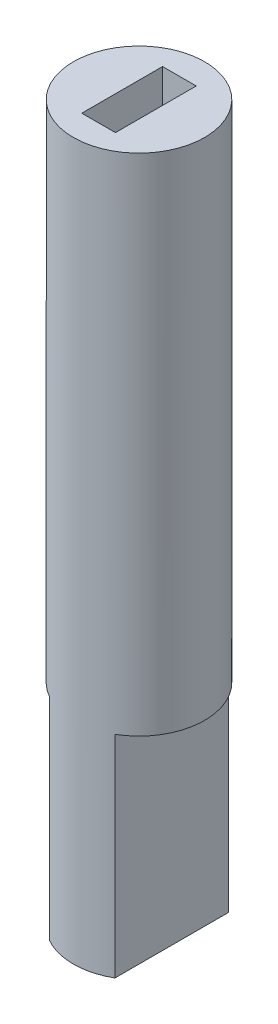
SolidWorks part; units mm, degrees
material "AISI 304"
ref_plane "Front Plane" through (0, 0, 0) normal (0, 0, 1) x (1, 0, 0)
ref_plane "Top Plane" through (0, 0, 0) normal (0, 1, 0) x (1, 0, 0)
ref_plane "Right Plane" through (0, 0, 0) normal (1, 0, 0) x (0, 0, -1)
sketch "Sketch1" plane through (0, 0, 0) normal (0, 1, 0) x (1, 0, 0)
  circle A0 centre (0, 0) radius 30
  dimension "D1" = 60
extrude "Boss-Extrude1" add sketch "Sketch1" along normal blind 200
sketch "Sketch2" plane through (0, 200, 0) normal (0, 1, 0) x (1, 0, 0)
  circle A0 centre (0, -50) radius 4
  circle A2 centre (0, 0) radius 30 construction
  dimension "D1" = 8
  dimension "D2" = 50
extrude "Boss-Extrude2" add sketch "Sketch2" against normal blind 80 from offset 60 separate body offset against normal yes
sketch "Sketch4" plane through (0, 140, 0) normal (0, 1, 0) x (1, 0, 0)
  line L6 (-2.9328, -47.28) -> (40.9159, 0)
  line L7 (2.9328, -52.72) -> (51.8267, 0)
  line L8 (40.9159, 0) -> (6, 37.6481)
  line L9 (51.8267, 0) -> (11.8657, 43.0881)
  line L10 (6, 37.6481) -> (11.8657, 43.0881)
  circle A0 centre (0, -50) radius 4 construction
  circle A1 centre (0, 0) radius 30 construction
  arc A2 (2.9328, -52.72) -> (-2.9328, -47.28) centre (0, -50) ccw
  dimension "D2" = 6
  dimension "D4" = 8
  dimension "D5" = 8
  dimension "D6" = 8
extrude "Boss-Extrude3" add sketch "Sketch4" against normal blind 10
sketch "Sketch5" plane through (0, 60, 0) normal (0, -1, 0) x (1, 0, 0)
  line L0 (6, -37.6481) -> (11.8657, -43.0881) construction
  line L1 (40.9159, 0) -> (6, -37.6481) construction
  line L2 (51.8267, 0) -> (11.8657, -43.0881) construction
  line L3 (2.9328, 52.72) -> (51.8267, 0) construction
  line L4 (-2.9328, 47.28) -> (40.9159, 0) construction
  line L5 (6, -37.6481) -> (11.8657, -43.0881)
  line L6 (40.9159, 0) -> (6, -37.6481)
  line L7 (51.8267, 0) -> (11.8657, -43.0881)
  line L8 (2.9328, 52.72) -> (51.8267, 0)
  line L9 (-2.9328, 47.28) -> (40.9159, 0)
  arc A0 (-2.9328, 47.28) -> (2.9328, 52.72) centre (0, 50) ccw construction
  arc A1 (-2.9328, 47.28) -> (2.9328, 52.72) centre (0, 50) ccw
extrude "Boss-Extrude4" add sketch "Sketch5" against normal blind 10
fillet "Fillet1" radius 10 4 edges at (51.8267, 65, 0) (40.9159, 65, 0) (40.9159, 135, 0) (51.8267, 135, 0)
fillet "Fillet2" radius 3 8 edges at (11.8657, 65, -43.0881) (8.9328, 70, -40.3681) (6, 65, -37.6481) (8.9328, 60, -40.3681) (6, 135, -37.6481) (8.9328, 130, -40.3681) (11.8657, 135, -43.0881) (8.9328, 140, -40.3681)
sketch "Sketch7" plane through (0, 140, 0) normal (0, 1, 0) x (1, 0, 0)
  circle A0 centre (0, -50) radius 4
extrude "Cut-Extrude1" cut sketch "Sketch7" against normal blind 12 from offset 34 offset against normal yes
sketch "Sketch8" plane through (0, 140, 0) normal (0, 1, 0) x (1, 0, 0)
  circle A0 centre (0, -50) radius 2
  dimension "D1" = 4
extrude "Cut-Extrude2" cut sketch "Sketch8" against normal blind 70
sketch "Sketch9" plane through (0, 140, 0) normal (0, 1, 0) x (1, 0, 0)
  circle A0 centre (0, -50) radius 2
extrude "Boss-Extrude6" add sketch "Sketch9" against normal blind 70 from offset 0.1
sketch "Sketch11" plane through (0, 140.1, 0) normal (0, 1, 0) x (1, 0, 0)
  line L0 (-0.975, -51.7462) -> (-0.975, -48.2538)
  line L1 (0.975, -48.2538) -> (0.975, -51.7462)
  circle A0 centre (0, -50) radius 2 construction
  circle A1 centre (0, -50) radius 2 construction
  arc A2 (-0.975, -48.2538) -> (-0.975, -51.7462) centre (0, -50) ccw
  arc A3 (0.975, -48.2538) -> (0.975, -51.7462) centre (0, -50) cw
  dimension "D3" = 2
  dimension "D4" = 2
  dimension "D1" = 1.95
  dimension "D2" = 0.975
extrude "Cut-Extrude4" cut sketch "Sketch11" against normal blind 35 from offset 30 offset against normal yes
sketch "Sketch12" plane through (0, 140.1, 0) normal (0, 1, 0) x (1, 0, 0)
  line L1 (-0.5, -48.8) -> (0.5, -48.8)
  line L2 (-0.5, -48.8) -> (-0.5, -51.2)
  line L3 (-0.5, -51.2) -> (0.5, -51.2)
  line L4 (0.5, -48.8) -> (0.5, -51.2)
  dimension "D1" = 0.5
  dimension "D2" = 0.5
  dimension "D3" = 1.2
  dimension "D4" = 2.4
extrude "Cut-Extrude5" cut sketch "Sketch12" against normal blind 20
sketch "Sketch14" plane through (0, 200, 0) normal (0, 1, 0) x (1, 0, 0)
  circle A0 centre (0, 0) radius 30
extrude "Cut-Extrude6" cut sketch "Sketch14" against normal blind 200
sketch "Sketch15" plane through (0, 140, 0) normal (0, 1, 0) x (1, 0, 0)
  circle A0 centre (0, -50) radius 2
  circle A1 centre (0, -50) radius 97.6896
  circle M2 centre (0, -50) radius 2
  line M3 (45.5203, 6.8) -> (13.9057, 40.8885)
  line M4 (13.9057, 40.8885) -> (8.04, 35.4485)
  line M5 (8.04, 35.4485) -> (34.6094, 6.8)
  arc M6 (34.6094, 6.8) -> (34.6094, -6.8) centre (27.2772, 0) cw
  line M7 (34.6094, -6.8) -> (-2.9328, -47.28)
  arc M8 (-2.9328, -47.28) -> (2.9328, -52.72) centre (0, -50) ccw
  line M9 (2.9328, -52.72) -> (45.5203, -6.8)
  arc M10 (45.5203, -6.8) -> (45.5203, 6.8) centre (38.1881, 0) ccw
extrude "Cut-Extrude7" cut sketch "Sketch15" against normal blind 200 contours A1 M3 M10 M9 M8 M7 M6 M5 M4 | M10 M3 M4 M5 M6 M7 M8 M9 M2 region at (-94.9265, 140, 50) region at (47.1052, 140, 0)
sketch "Sketch16" plane through (0.975, 0, 0) normal (1, 0, 0) x (0, 0, -1)
  line L1 (-52, 70) -> (-46.8505, 70)
  line L2 (-52, 70) -> (-52, 58.4746)
  line L3 (-52, 58.4746) -> (-46.8505, 58.4746)
  line L4 (-46.8505, 70) -> (-46.8505, 58.4746)
extrude "Cut-Extrude8" cut sketch "Sketch16" against normal blind 200 and the other way blind 200
sketch "Sketch17" plane through (-0.975, 0, 0) normal (-1, 0, 0) x (0, 0, 1)
  line L0 (48, 140.1) -> (48, 70.1) construction
  line L1 (48, 75.1) -> (52, 75.1)
  line L2 (48, 75.1) -> (48, 70.1)
  line L3 (48, 70.1) -> (52, 70.1)
  line L4 (52, 75.1) -> (52, 70.1)
extrude "Cut-Extrude9" cut sketch "Sketch17" against normal blind 200 and the other way blind 200
sketch "Sketch18" plane through (0, 75.1, 0) normal (0, -1, 0) x (1, 0, 0)
  line L1 (-3.2384, 53.2582) -> (3.7803, 53.2582)
  line L2 (-3.2384, 53.2582) -> (-3.2384, 46.6492)
  line L3 (-3.2384, 46.6492) -> (3.7803, 46.6492)
  line L4 (3.7803, 53.2582) -> (3.7803, 46.6492)
sketch "Sketch19" plane through (0, 140.1, 0) normal (0, 1, 0) x (1, 0, 0)
  line L5 (2.3255, -54.0726) -> (-5.7485, -54.0726)
  line L6 (2.3255, -54.0726) -> (2.3255, -40.8564)
  line L7 (2.3255, -40.8564) -> (-5.7485, -40.8564)
  line L8 (-5.7485, -54.0726) -> (-5.7485, -40.8564)
extrude "Cut-Extrude11" cut sketch "Sketch19" against normal blind 7
sketch "Sketch20" plane through (0, 133.1, 0) normal (0, 1, 0) x (1, 0, 0)
  line L1 (-7.0967, -41.6443) -> (9.8125, -41.6443)
  line L2 (-7.0967, -41.6443) -> (-7.0967, -59.4434)
  line L3 (-7.0967, -59.4434) -> (9.8125, -59.4434)
  line L4 (9.8125, -41.6443) -> (9.8125, -59.4434)
extrude "Cut-Extrude12" cut sketch "Sketch20" against normal blind 3
sketch "Sketch21" plane through (0, 75.1, 0) normal (0, -1, 0) x (1, 0, 0)
  line L1 (7.3278, 44.4932) -> (-11.381, 44.4932)
  line L2 (7.3278, 44.4932) -> (7.3278, 60.5134)
  line L3 (7.3278, 60.5134) -> (-11.381, 60.5134)
  line L4 (-11.381, 44.4932) -> (-11.381, 60.5134)
extrude "Cut-Extrude13" cut sketch "Sketch21" against normal blind 3
sketch "Sketch22" plane through (0, 78.1, 0) normal (0, -1, 0) x (1, 0, 0)
  line L1 (-4.243, 53.2054) -> (4.3619, 53.2054)
  line L2 (-4.243, 53.2054) -> (-4.243, 47.2705)
  line L3 (-4.243, 47.2705) -> (4.3619, 47.2705)
  line L4 (4.3619, 53.2054) -> (4.3619, 47.2705)
extrude "Cut-Extrude14" cut sketch "Sketch22" against normal blind 30.73
sketch "Sketch23" plane through (0, 110.1, 0) normal (0, -1, 0) x (1, 0, 0)
  line L0 (-0.975, 51.7462) -> (-0.975, 48.2538) construction
  line L1 (-0.975, 51.7462) -> (-0.975, 48.2538)
  line L2 (0.975, 48.2538) -> (0.975, 51.7462) construction
  line L3 (0.975, 48.2538) -> (0.975, 51.7462)
  arc A0 (-0.975, 51.7462) -> (-0.975, 48.2538) centre (0, 50) ccw construction
  arc A1 (-0.975, 51.7462) -> (-0.975, 48.2538) centre (0, 50) ccw
  arc A2 (0.975, 48.2538) -> (0.975, 51.7462) centre (0, 50) ccw construction
  arc A3 (0.975, 48.2538) -> (0.975, 51.7462) centre (0, 50) ccw
extrude "Cut-Extrude15" cut sketch "Sketch23" against normal blind 5
sketch "Sketch24" plane through (0, 130.1, 0) normal (0, 1, 0) x (1, 0, 0)
  circle A0 centre (0, -50) radius 2 construction
  circle A1 centre (0, -50) radius 2
  circle A2 centre (0, -50) radius 1.95
  dimension "D1" = 0.05
extrude "Cut-Extrude16" cut sketch "Sketch24" against normal blind 25
